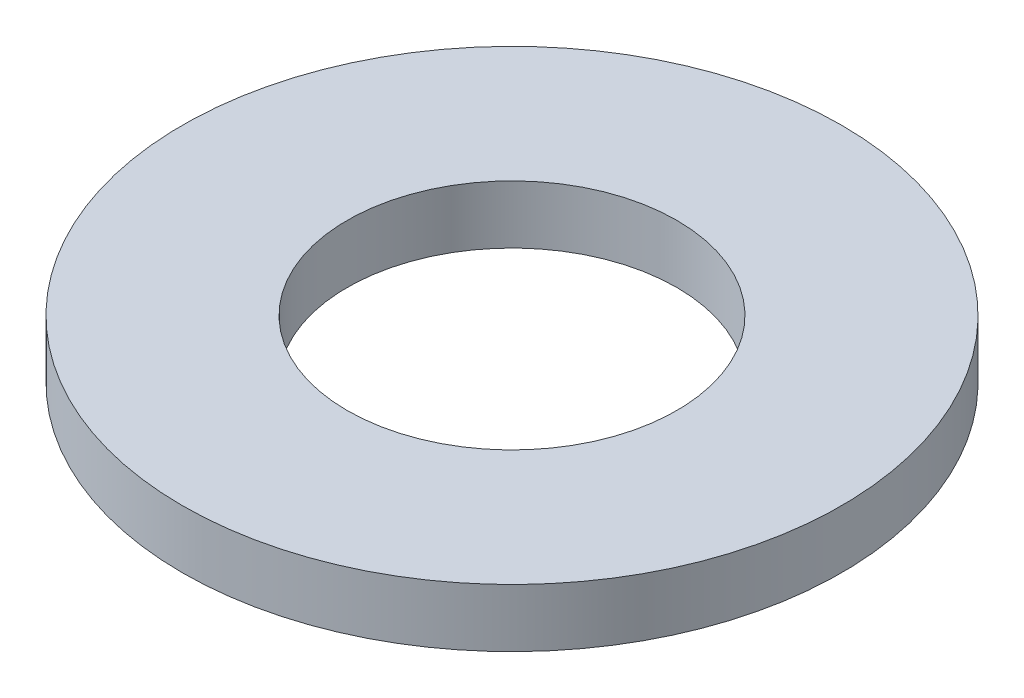
SolidWorks part; units mm, degrees
ref_plane "Front Plane" through (0, 0, 0) normal (0, 0, 1) x (1, 0, 0)
ref_plane "Top Plane" through (0, 0, 0) normal (0, 1, 0) x (1, 0, 0)
ref_plane "Right Plane" through (0, 0, 0) normal (1, 0, 0) x (0, 0, -1)
sketch "Sketch1" plane through (0, 0, 0) normal (0, 1, 0) x (1, 0, 0)
  circle A0 centre (0, 0) radius 85
  dimension "FLANGE_OD" = 170
extrude "Boss-Extrude1" add sketch "Sketch1" along normal blind 15
sketch "Sketch2" plane through (0, 0, 0) normal (0, 1, 0) x (1, 0, 0)
  circle A0 centre (0, 0) radius 42.5
  dimension "BORE_D" = 85
extrude "Cut-Extrude1" cut sketch "Sketch2" along normal through all
sketch "Sketch3" plane through (0, 15, 0) normal (0, 1, 0) x (1, 0, 0)
  circle A0 centre (0, 0) radius 37.6117 construction
  circle A1 centre (-37.6117, 0) radius 3.7024
  dimension "BOLT_D" = 7.4047
  dimension "BOLT_PCD" = 75.2233
extrude "Cut-Extrude2" cut sketch "Sketch3" against normal blind 11.7554 rebuild error yes
pattern_circular "CirPattern1" count 4 over 360 rebuild error yes
